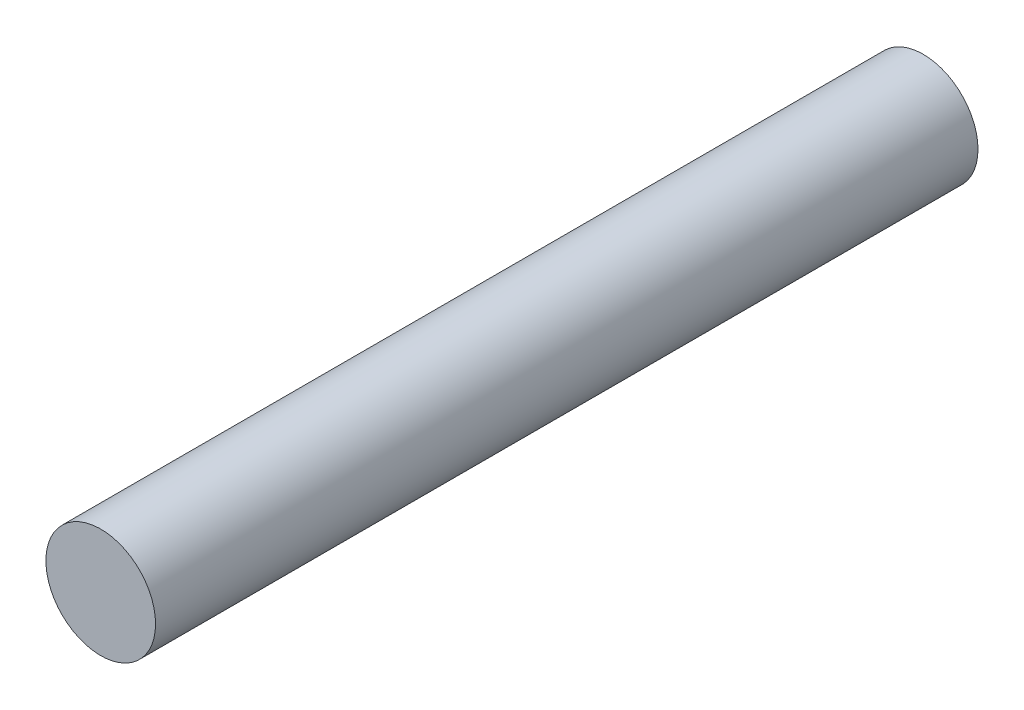
SolidWorks part; units mm, degrees
ref_plane "Front Plane" through (0, 0, 0) normal (0, 0, 1) x (1, 0, 0)
ref_plane "Top Plane" through (0, 0, 0) normal (0, 1, 0) x (1, 0, 0)
ref_plane "Right Plane" through (0, 0, 0) normal (1, 0, 0) x (0, 0, -1)
sketch "Sketch1" plane through (0, 0, 0) normal (0, 1, 0) x (1, 0, 0)
  line L0 (0, -48.7094) -> (0, -46.4499) construction
  line L1 (-4, 0) -> (0, 0)
  line L2 (-4, 0) -> (-4, -60)
  line L3 (-4, -60) -> (0, -60)
  line L4 (0, 0) -> (0, -60)
  dimension "D1" = 8
  dimension "D2" = 60
revolve "Revolve1" add sketch "Sketch1" angle 360 about L0
ref_axis "Axis1" through (0, 0, 63) along (0, 0, -1)
